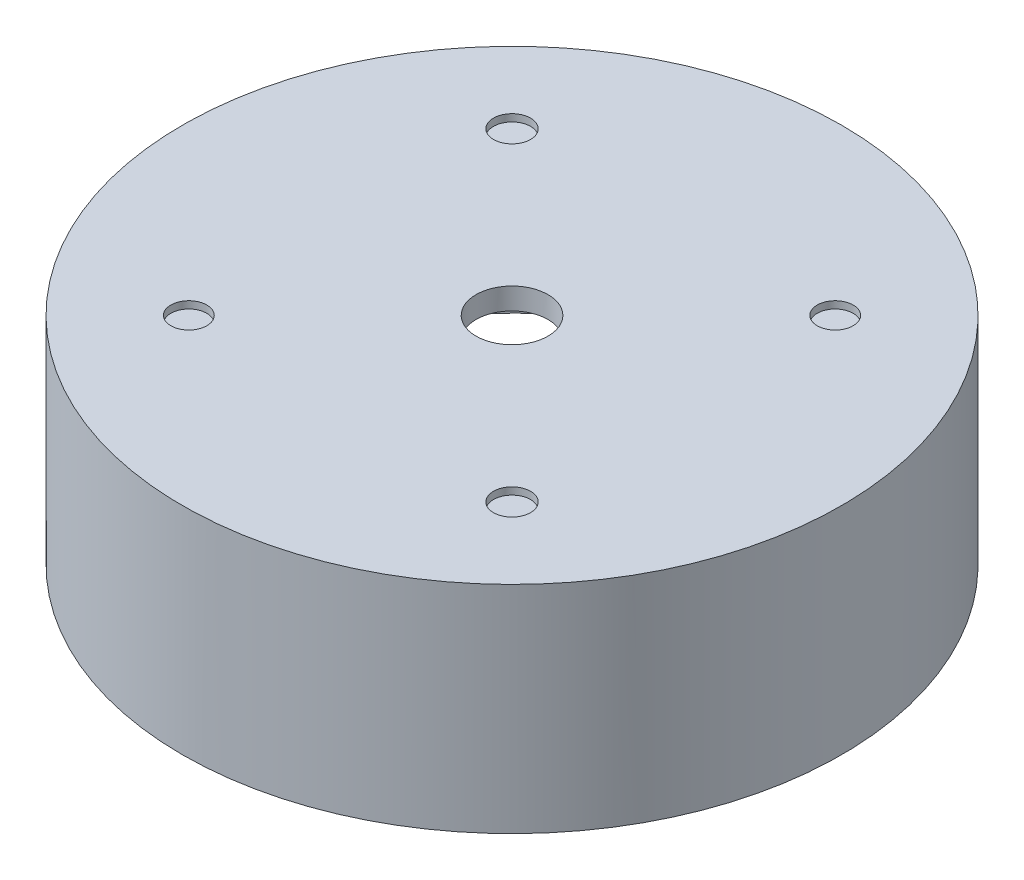
SolidWorks part; units mm, degrees
ref_plane "Alzado" through (0, 0, 0) normal (0, 0, 1) x (1, 0, 0)
ref_plane "Planta" through (0, 0, 0) normal (0, 1, 0) x (1, 0, 0)
ref_plane "Vista lateral" through (0, 0, 0) normal (1, 0, 0) x (0, 0, -1)
sketch "Croquis5" plane through (0, 0, 0) normal (0, 0, 1) x (1, 0, 0)
  line L1 (0, 0) -> (33.22, 0)
  line L2 (33.22, 0) -> (45.8065, 15)
  line L3 (45.8065, 15) -> (45.8065, 50)
  line L4 (45.8065, 50) -> (0, 50)
  line L6 (45.8065, 15) -> (45.8065, 0) construction
  line L7 (45.8065, 0) -> (33.22, 0) construction
  line L8 (0, 0) -> (0, 3)
  line L9 (0, 3) -> (31.8211, 3)
  line L10 (31.8211, 3) -> (42.8065, 16.0919)
  line L11 (42.8065, 16.0919) -> (42.8065, 47)
  line L12 (42.8065, 47) -> (0, 47)
  line L13 (0, 47) -> (0, 50)
  line L14 (0, 0) -> (0, 65.0712) construction
  dimension "D1" = 50
  dimension "D2" = 50
  dimension "D3" = 15
  dimension "D4" = 33.22
  dimension "D5" = 3
  dimension "D6" = 3
  dimension "D7" = 3
  dimension "D8" = 3
revolve "Revolución2" add sketch "Croquis5" angle 360 about L14
sketch "Croquis7" plane through (0, 50, 0) normal (0, 1, 0) x (1, 0, 0)
  line L5 (-25, 25) -> (25, 25)
  line L6 (-25, 25) -> (-25, -25)
  line L7 (-25, -25) -> (25, -25)
  line L8 (25, 25) -> (25, -25)
  line L9 (-25, 25) -> (25, -25) construction
  line L10 (-25, -25) -> (25, 25) construction
  point P0 (0, 0)
  dimension "D1" = 50
  dimension "D2" = 50
extrude "Saliente-Extruir3" add sketch "Croquis7" along normal blind 120
sketch "Croquis10" plane through (0, 0, 25) normal (0, 0, 1) x (1, 0, 0)
  line L0 (-25, 50) -> (-3.8408, 170)
  line L1 (-25, 170) -> (25, 170) construction
  line L2 (-3.8408, 170) -> (-25, 170)
  line L3 (-25, 170) -> (-25, 50)
  line L4 (25, 50) -> (25, 170)
  line L5 (25, 170) -> (3.8408, 170)
  line L6 (3.8408, 170) -> (25, 50)
  dimension "D1" = 10
  dimension "D2" = 10
extrude "Cortar-Extruir6" cut sketch "Croquis10" against normal through all
sketch "Croquis11" plane through (0, 0, 0) normal (1, 0, 0) x (0, 0, -1)
  line L0 (-25, 50) -> (-3.8408, 170)
  line L1 (25, 170) -> (-25, 170) construction
  line L2 (-3.8408, 170) -> (-25, 170)
  line L3 (-25, 170) -> (-25, 50)
  line L4 (25, 50) -> (25, 170)
  line L5 (25, 170) -> (3.8408, 170)
  line L6 (3.8408, 170) -> (25, 50)
  dimension "D1" = 10
  dimension "D2" = 10
extrude "Cortar-Extruir7" cut sketch "Croquis11" against normal through all both and the other way through all
sketch "Croquis12" plane through (0, 0, 0) normal (0, 0, 1) x (1, 0, 0)
  line L0 (-19.9229, 50) -> (19.9229, 50)
  line L1 (-25, 50) -> (25, 50) construction
  line L2 (19.9229, 50) -> (2.2902, 150)
  line L3 (2.2902, 150) -> (-2.2902, 150)
  line L4 (-2.2902, 150) -> (-19.9229, 50)
  line L7 (-25, 50) -> (-3.8408, 170) construction
  line L8 (3.8408, 170) -> (25, 50) construction
  dimension "D1" = 5
  dimension "D2" = 5
  dimension "D3" = 100
extrude "Cortar-Extruir8" cut sketch "Croquis12" against normal through all both and the other way through all
sketch "Croquis13" plane through (0, 0, 0) normal (1, 0, 0) x (0, 0, -1)
  line L0 (-19.9229, 50) -> (19.9229, 50)
  line L1 (-25, 50) -> (25, 50) construction
  line L2 (19.9229, 50) -> (2.2902, 150)
  line L3 (2.2902, 150) -> (-2.2902, 150)
  line L4 (-2.2902, 150) -> (-19.9229, 50)
  line L5 (-3.8408, 170) -> (-25, 50) construction
  line L6 (25, 50) -> (3.8408, 170) construction
  dimension "D1" = 5
  dimension "D2" = 5
  dimension "D3" = 100
extrude "Cortar-Extruir9" cut sketch "Croquis13" against normal through all both and the other way through all
fillet "Redondeo1" radius 2.5 16 edges at (-11.1065, 100, -11.1065) (-11.1065, 100, -16.1837) (-14.4204, 110, -14.4204) (-16.1837, 100, -11.1065) (11.1065, 100, -11.1065) (16.1837, 100, -11.1065) (14.4204, 110, -14.4204) (11.1065, 100, -16.1837) (11.1065, 100, 11.1065) (11.1065, 100, 16.1837) (14.4204, 110, 14.4204) (16.1837, 100, 11.1065) (-11.1065, 100, 11.1065) (-11.1065, 100, 16.1837) (-16.1837, 100, 11.1065) (-14.4204, 110, 14.4204)
sketch "Croquis15" plane through (0, 0, 0) normal (0, 0, 1) x (1, 0, 0)
  line L0 (45.8065, 50) -> (-45.8065, 50) construction
  line L1 (-53.4023, 20) -> (58.991, 20)
  line L2 (-53.4023, 20) -> (-53.4023, -24.7089)
  line L3 (-53.4023, -24.7089) -> (58.991, -24.7089)
  line L4 (58.991, 20) -> (58.991, -24.7089)
  dimension "D1" = 30
extrude "Cortar-Extruir10" cut sketch "Croquis15" against normal through all both and the other way through all
thread "Rosca2" pitch 2.5 method extrude profile "Perfil de rosca2" start angle 0, offset 0, length 17, pitch 2.5, diameter 85.613
ref_plane "Plano2" through (42.8065, 20, 0) normal (0, 0, 1) x (1, 0, 0)
sketch "Perfil de rosca2" plane through (42.8065, 20, 0) normal (0, 0, 1) x (1, 0, 0)
  line L0 (0, 0) -> (0, 2.5) construction
  line L11 (0, 0) -> (0, 2.1875)
  line L12 (0, 2.1875) -> (-1.3532, 1.4062)
  line L13 (-1.3532, 1.4062) -> (-1.3532, 0.7812)
  line L15 (-1.3532, 0.7812) -> (0, 0)
  line L17 (-1.3532, 1.0937) -> (0, 1.0937) construction
  point P2 (0, 0)
  dimension "Pitch" = 2.5
  dimension "Profile_Angle" = 60
  dimension "Profile_Land" = 0.625
  dimension "Profile_Height" = 1.3532
sketch "Croquis20" plane through (0, 0, 0) normal (0, 0, 1) x (1, 0, 0)
  line L0 (45.8065, 50) -> (-45.8065, 50) construction
  line L1 (-45.8065, 50) -> (45.8065, 50)
  line L2 (-45.8065, 50) -> (-45.8065, 174.0856)
  line L3 (-45.8065, 174.0856) -> (45.8065, 174.0856)
  line L4 (45.8065, 50) -> (45.8065, 174.0856)
extrude "Cortar-Extruir16" cut sketch "Croquis20" against normal through all both and the other way through all
sketch "Croquis16" plane through (0, 50, 0) normal (0, 1, 0) x (1, 0, 0)
  circle A4 centre (-22.4614, 22.4614) radius 2.5766
  circle A5 centre (-22.4614, -22.4614) radius 2.5
  circle A6 centre (22.4614, -22.4614) radius 2.5766
  circle A7 centre (22.4614, 22.4614) radius 2.5
extrude "Cortar-Extruir17" cut sketch "Croquis16" against normal blind 1
sketch "Croquis21" plane through (0, 50, 0) normal (0, 1, 0) x (1, 0, 0)
  circle A0 centre (0, 0) radius 5
  dimension "D1" = 10
extrude "Cortar-Extruir18" cut sketch "Croquis21" against normal up to next
